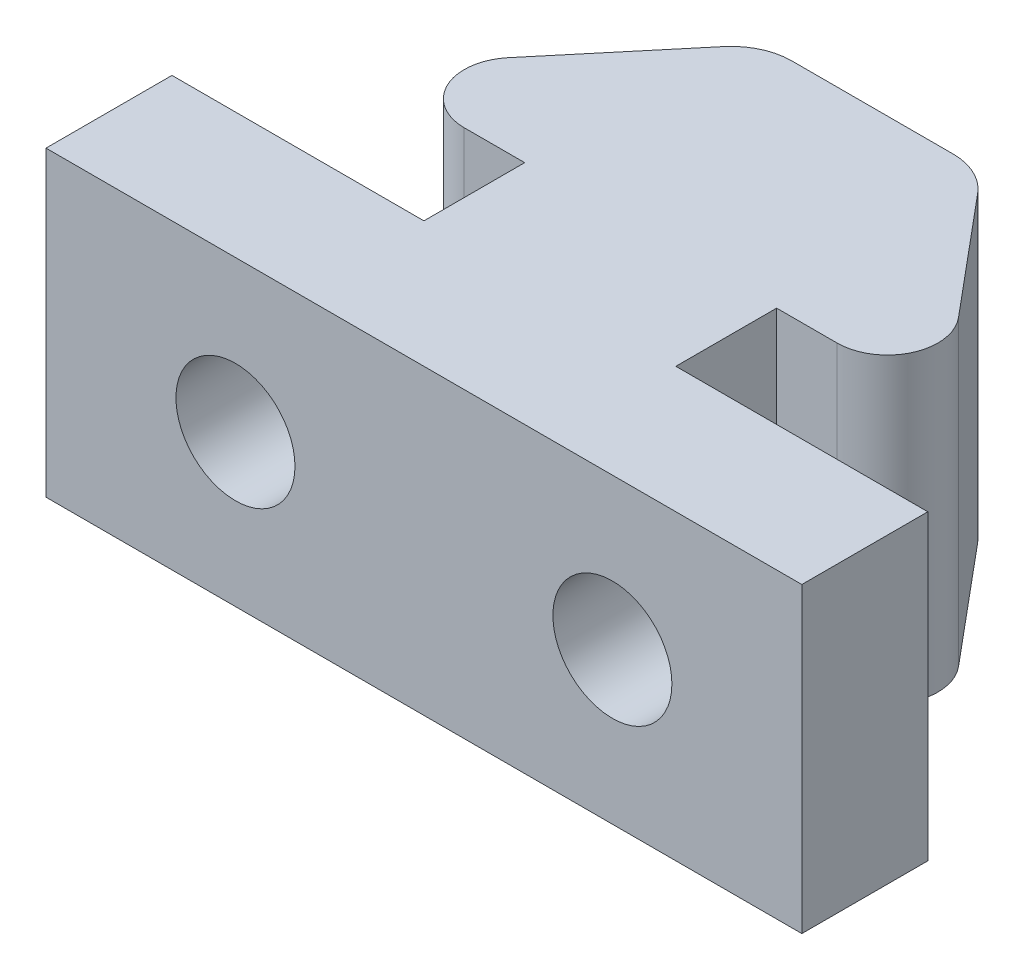
SolidWorks part; units mm, degrees
ref_plane "Front Plane" through (0, 0, 0) normal (0, 0, 1) x (1, 0, 0)
ref_plane "Top Plane" through (0, 0, 0) normal (0, 1, 0) x (1, 0, 0)
ref_plane "Right Plane" through (0, 0, 0) normal (1, 0, 0) x (0, 0, -1)
sketch "Sketch1" plane through (0, 0, 0) normal (0, 0, 1) x (1, 0, 0)
  line L0 (-9.525, 0) -> (9.525, 0) construction
  line L1 (-9.525, -3.81) -> (9.525, -3.81)
  line L2 (-9.525, -3.81) -> (-9.525, 3.81)
  line L3 (-9.525, 3.81) -> (9.525, 3.81)
  line L4 (9.525, -3.81) -> (9.525, 3.81)
  line L5 (-9.525, -3.81) -> (9.525, 3.81) construction
  line L6 (-9.525, 3.81) -> (9.525, -3.81) construction
  line L8 (-9.525, 3.81) -> (0, 3.81)
  point P0 (0, 0)
  dimension "D1" = 7.62
  dimension "D2" = 19.05
extrude "Boss-Extrude1" add sketch "Sketch1" along normal blind 3.175 contours L2 L1 L4 L3
sketch "Sketch2" plane through (0, 3.81, 0) normal (0, 1, 0) x (1, 0, 0)
  line L0 (0, 0) -> (0, 8.128) construction
  line L1 (3.175, 0) -> (3.175, 2.54)
  line L2 (-9.525, 0) -> (9.525, 0) construction
  line L3 (3.175, 2.54) -> (4.6994, 2.54)
  line L4 (5.6737, 4.6247) -> (3.2011, 7.5816)
  line L5 (2.032, 8.128) -> (-2.032, 8.128)
  line L6 (3.175, 0) -> (-3.175, 0)
  line L7 (-3.175, 0) -> (-3.175, 2.54)
  line L8 (-3.175, 2.54) -> (-4.6994, 2.54)
  line L9 (-5.6737, 4.6247) -> (-3.2011, 7.5816)
  arc A0 (3.2011, 7.5816) -> (2.032, 8.128) centre (2.032, 6.604) ccw
  arc A1 (4.6994, 2.54) -> (5.6737, 4.6247) centre (4.6994, 3.81) ccw
  arc A2 (-4.6994, 2.54) -> (-5.6737, 4.6247) centre (-4.6994, 3.81) cw
  arc A3 (-3.2011, 7.5816) -> (-2.032, 8.128) centre (-2.032, 6.604) cw
  point P19 (2.7442, 8.128)
  point P22 (7.4168, 2.54)
  point P25 (-7.4168, 2.54)
  point P28 (-2.7442, 8.128)
  dimension "D5" = 1.524
  dimension "D7" = 1.27
  dimension "D1" = 8.128
  dimension "D2" = 6.35
  dimension "D3" = 5.588
  dimension "D4" = 14.8336
  dimension "D6" = 4.064
extrude "Boss-Extrude2" add sketch "Sketch2" against normal up to surface (7.62 mm away) up to face at (0, -3.81, 1.5875)
sketch "Sketch3" plane through (0, 0, 3.175) normal (0, 0, 1) x (1, 0, 0)
  line L0 (0, 3.81) -> (0, -3.81) construction
  line L1 (-9.525, 3.81) -> (9.525, 3.81) construction
  line L2 (-9.525, -3.81) -> (9.525, -3.81) construction
  circle A0 centre (-4.75, 0) radius 1.5
  circle A1 centre (4.75, 0) radius 1.5
  dimension "D2" = 3
  dimension "D1" = 9.5
extrude "Cut-Extrude1" cut sketch "Sketch3" against normal up to surface (3.175 mm away) up to face at (6.35, 0, 0)
